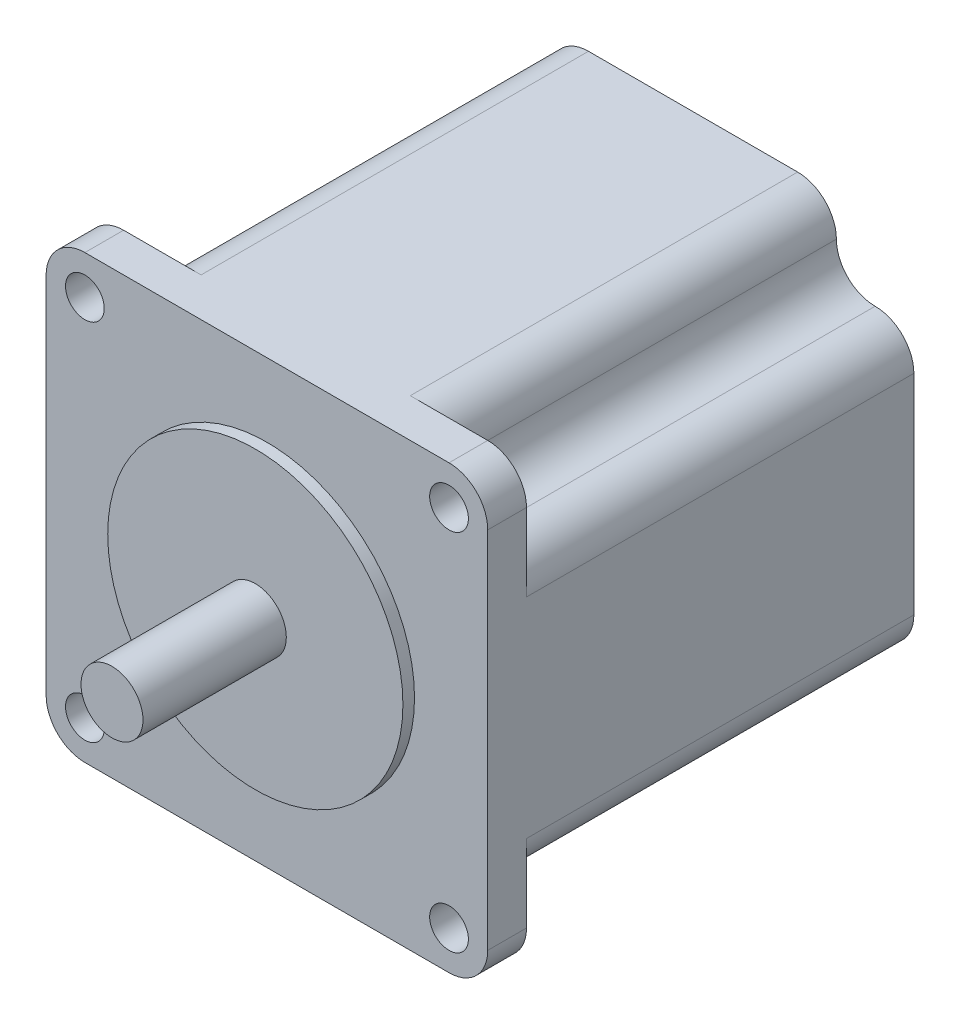
SolidWorks part; units mm, degrees
ref_plane "Front Plane" through (0, 0, 0) normal (0, 0, 1) x (1, 0, 0)
ref_plane "Top Plane" through (0, 0, 0) normal (0, 1, 0) x (1, 0, 0)
ref_plane "Right Plane" through (0, 0, 0) normal (1, 0, 0) x (0, 0, -1)
sketch "Sketch1" plane through (0, 0, 0) normal (0, 0, 1) x (1, 0, 0)
  line L1 (-33.3612, 31.2642) -> (23.6388, 31.2642)
  line L2 (-33.3612, 31.2642) -> (-33.3612, -25.7358)
  line L3 (-33.3612, -25.7358) -> (23.6388, -25.7358)
  line L4 (23.6388, 31.2642) -> (23.6388, -25.7358)
  dimension "D1" = 57
  dimension "D2" = 57
extrude "Boss-Extrude1" add sketch "Sketch1" along normal blind 55
sketch "Sketch2" plane through (0, 0, 0) normal (0, 0, -1) x (-1, 0, 0)
  line L1 (-23.6388, 31.2642) -> (-13.6388, 31.2642)
  line L2 (-23.6388, 31.2642) -> (-23.6388, 21.2642)
  line L3 (-23.6388, 21.2642) -> (-13.6388, 21.2642)
  line L4 (-13.6388, 31.2642) -> (-13.6388, 21.2642)
  dimension "D1" = 10
  dimension "D2" = 10
extrude "Cut-Extrude1" cut sketch "Sketch2" against normal blind 50
pattern_linear "LPattern1" count 2 spacing 47 along (-1, 0, 0) count 2 spacing 47 along (0, -1, 0) of "Cut-Extrude1"
sketch "Sketch3" plane through (0, 0, 55) normal (0, 0, 1) x (1, 0, 0)
  line L0 (23.6388, 31.2642) -> (-33.3612, 31.2642) construction
  line L1 (-33.3612, 31.2642) -> (-33.3612, -25.7358) construction
  circle A0 centre (-28.3612, 26.2642) radius 2.5
  dimension "D3" = 5
  dimension "D1" = 5
  dimension "D2" = 5
extrude "Cut-Extrude2" cut sketch "Sketch3" against normal blind 50
pattern_linear "LPattern2" count 2 spacing 47 along (1, 0, 0) count 2 spacing 47 along (0, -1, 0) of "Cut-Extrude2"
fillet "Fillet1" radius 5 16 edges at (-33.3612, 21.2642, 25) (-23.3612, 21.2642, 25) (-23.3612, 31.2642, 25) (13.6388, 31.2642, 25) (13.6388, 21.2642, 25) (23.6388, 21.2642, 25) (23.6388, -25.7358, 52.5) (23.6388, -15.7358, 25) (13.6388, -15.7358, 25) (13.6388, -25.7358, 25) (-23.3612, -25.7358, 25) (-23.3612, -15.7358, 25) (-33.3612, -15.7358, 25) (-33.3612, -25.7358, 52.5) (-33.3612, 31.2642, 52.5) (23.6388, 31.2642, 52.5)
sketch "Sketch5" plane through (0, 0, 55) normal (0, 0, 1) x (1, 0, 0)
  line L0 (18.6388, 31.2642) -> (-28.3612, 31.2642) construction
  line L1 (-33.3612, 26.2642) -> (-33.3612, -20.7358) construction
  circle A0 centre (-4.8612, 2.7642) radius 19.05
  dimension "D1" = 28.5
  dimension "D2" = 28.5
extrude "Boss-Extrude3" add sketch "Sketch5" along normal blind 1.5
sketch "Sketch4" plane through (0, 0, 55) normal (0, 0, 1) x (1, 0, 0)
  line L0 (18.6388, 31.2642) -> (-28.3612, 31.2642) construction
  line L1 (23.6388, -20.7358) -> (23.6388, 26.2642) construction
  circle A0 centre (-4.8612, 2.7642) radius 4
  dimension "D3" = 8
  dimension "D1" = 28.5
  dimension "D2" = 28.5
extrude "Boss-Extrude2" add sketch "Sketch4" along normal blind 20
